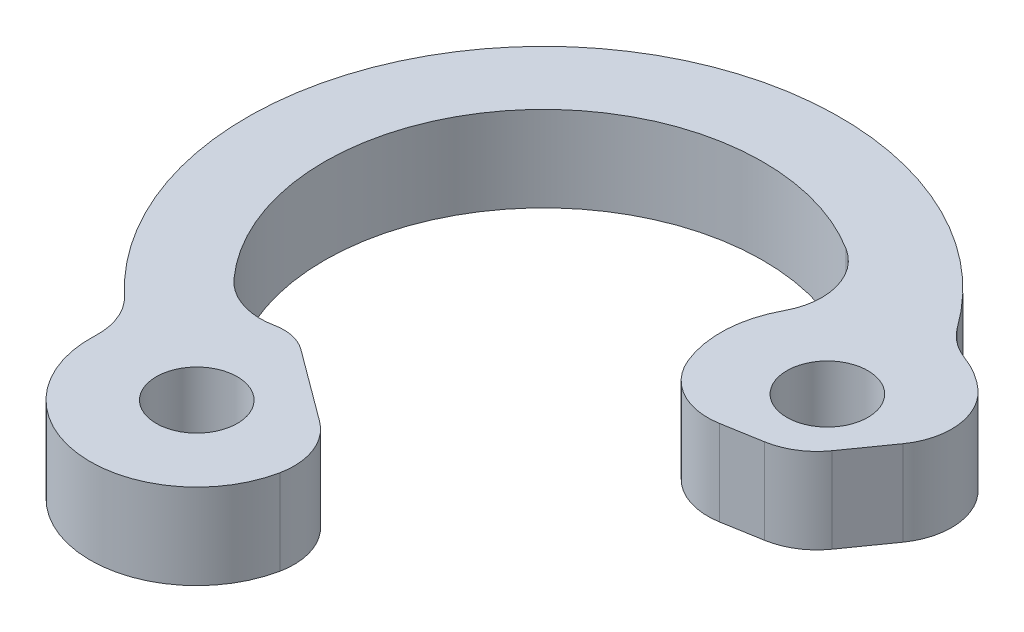
SolidWorks part; units mm, degrees
ref_plane "Front Plane" through (0, 0, 0) normal (0, 0, 1) x (1, 0, 0)
ref_plane "Top Plane" through (0, 0, 0) normal (0, 1, 0) x (1, 0, 0)
ref_plane "Right Plane" through (0, 0, 0) normal (1, 0, 0) x (0, 0, -1)
sketch "Sketch2" plane through (0, 0, 0) normal (0, 1, 0) x (1, 0, 0)
  circle A3 centre (87.0735, 81.0463) radius 1.9
  circle A5 centre (72.5387, 66.0204) radius 1.9
  arc A9 (84.158, 85.1082) -> (87.9596, 85.9672) centre (87.0735, 81.0463) ccw
  arc A10 (67.7859, 67.5732) -> (70.0824, 70.3755) centre (72.5387, 66.0204) ccw
  arc A16 (84.158, 85.1082) -> (70.0824, 70.3755) centre (76.1332, 78.6848) ccw
  arc A18 (87.9715, 85.965) -> (67.7859, 67.5732) centre (76.1332, 78.6848) ccw
extrude "Boss-Extrude1" add sketch "Sketch2" along normal blind 4 contours A18 A16 A3 A5 region at (68.387, 0, -86.0855)
fillet "Fillet1" radius 3 4 edges at (67.7859, 2, -67.5732) (70.0824, 2, -70.3755) (84.158, 2, -85.1082) (87.9715, 2, -85.965)
sketch "Sketch4" plane through (0, 0, 0) normal (0, -1, 0) x (-1, 0, 0)
  line L0 (-78.0637, 66.7167) -> (-72.145, 71.0915)
  line L1 (-72.145, 71.0915) -> (-73.0772, 72.3527)
  line L2 (-73.0772, 72.3527) -> (-78.9959, 67.9779)
  line L3 (-78.9959, 67.9779) -> (-78.0637, 66.7167)
extrude "Cut-Extrude2" cut sketch "Sketch4" against normal blind 7
fillet "Fillet2" radius 3 1 edges at (77.3948, 2, -67.211)
fillet "Fillet3" radius 2 1 edges at (72.2523, 2, -71.0122)
sketch "Sketch5" plane through (0, 4, 0) normal (0, 1, 0) x (1, 0, 0)
  line L0 (91.9157, 82.2928) -> (87.5095, 76.0653)
  line L1 (91.9157, 82.2928) -> (94.0459, 81.0848)
  line L2 (94.0459, 81.0848) -> (89.2486, 74.6155)
  line L3 (89.2486, 74.6155) -> (87.5095, 76.0653)
  arc A0 (82.6696, 83.4139) -> (88.8113, 85.7346) centre (87.0735, 81.0463) ccw construction
extrude "Cut-Extrude3" cut sketch "Sketch5" against normal blind 4
fillet "Fillet4" radius 3 2 edges at (87.5095, 2, -76.0653) (91.9157, 2, -82.2928)
sketch "Sketch6" plane through (0, 4, 0) normal (0, 1, 0) x (1, 0, 0)
  line L0 (88.77, 77.8469) -> (84.083, 77.0392)
  line L1 (90.8599, 80.8006) -> (88.5653, 77.5575) construction
  line L2 (84.083, 77.0392) -> (84.6593, 75.3461)
  line L3 (84.6593, 75.3461) -> (89.0906, 75.9868)
  line L4 (89.0906, 75.9868) -> (88.77, 77.8469)
  arc A0 (82.6696, 83.4139) -> (84.6804, 76.6562) centre (87.0735, 81.0463) ccw construction
extrude "Cut-Extrude4" cut sketch "Sketch6" against normal blind 5
fillet "Fillet5" radius 3 2 edges at (84.083, 2, -77.0392) (88.77, 2, -77.8469)
